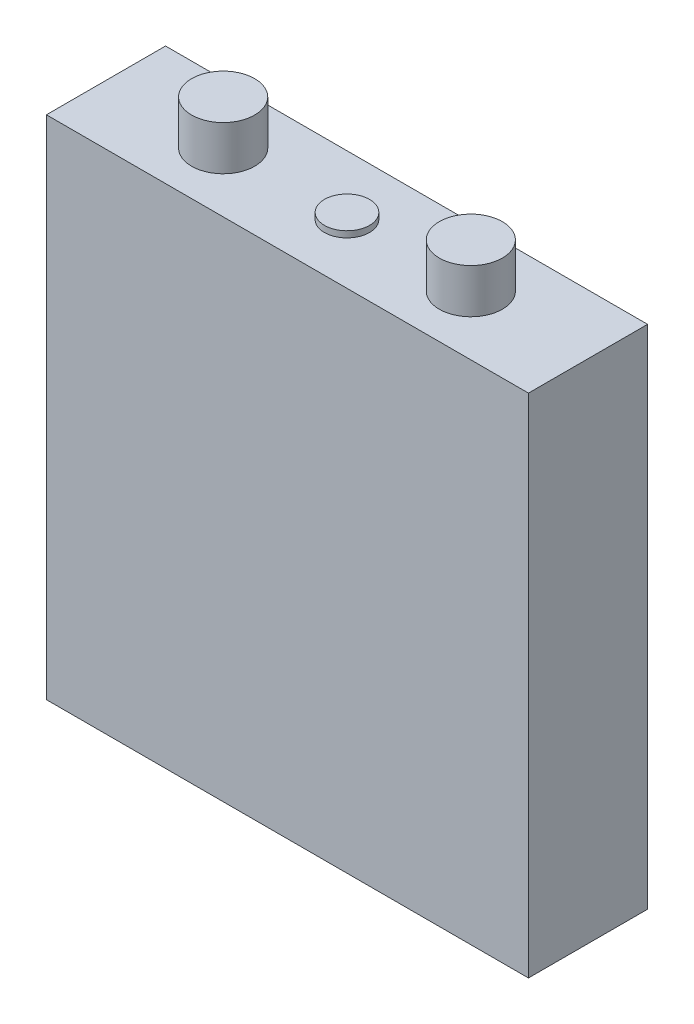
SolidWorks part; units mm, degrees
ref_plane "Front Plane" through (0, 0, 0) normal (0, 0, 1) x (1, 0, 0)
ref_plane "Top Plane" through (0, 0, 0) normal (0, 1, 0) x (1, 0, 0)
ref_plane "Right Plane" through (0, 0, 0) normal (1, 0, 0) x (0, 0, -1)
sketch "Sketch1" plane through (0, 0, 0) normal (0, 1, 0) x (1, 0, 0)
  line L1 (-2717, 671.5) -> (2717, 671.5)
  line L2 (-2717, 671.5) -> (-2717, -671.5)
  line L3 (-2717, -671.5) -> (2717, -671.5)
  line L4 (2717, 671.5) -> (2717, -671.5)
  line L5 (-2717, 671.5) -> (2717, -671.5) construction
  line L6 (-2717, -671.5) -> (2717, 671.5) construction
  point P0 (0, 0)
  dimension "D1" = 5434
  dimension "D2" = 1343
extrude "Boss-Extrude1" add sketch "Sketch1" along normal blind 5710
sketch "Sketch2" plane through (0, 5710, 0) normal (0, 1, 0) x (1, 0, 0)
  circle A0 centre (-1396, 0) radius 355.6
  circle A1 centre (1396, 0) radius 355.6
extrude "Boss-Extrude2" add sketch "Sketch2" along normal blind 500 contours A0 | A1
sketch "Sketch3" plane through (0, 5710, 0) normal (0, 1, 0) x (1, 0, 0)
  circle A0 centre (0, 0) radius 254
extrude "Boss-Extrude3" add sketch "Sketch3" along normal blind 70
